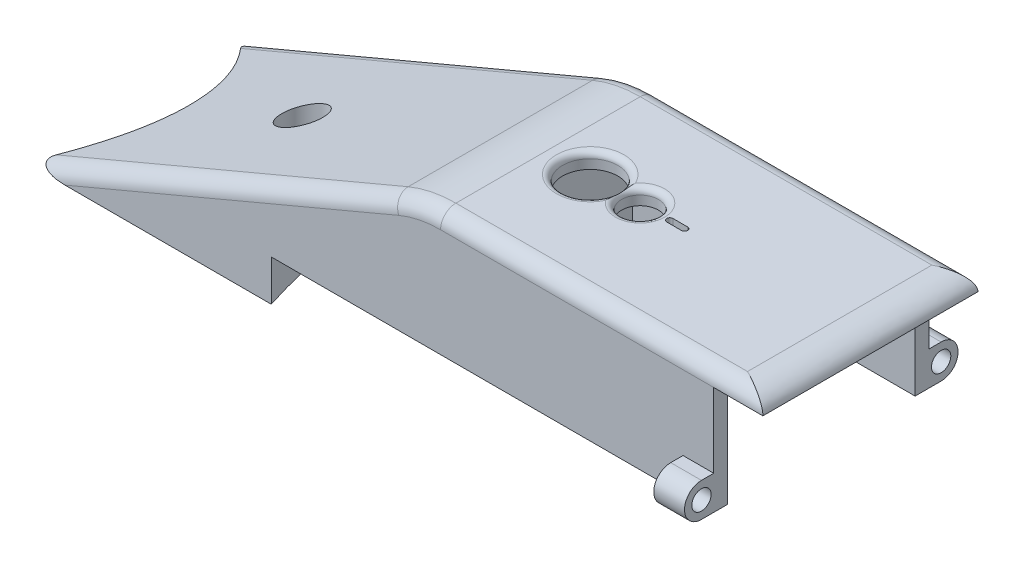
SolidWorks part; units mm, degrees
ref_plane "Front Plane" through (0, 0, 0) normal (0, 0, 1) x (1, 0, 0)
ref_plane "Top Plane" through (0, 0, 0) normal (0, 1, 0) x (1, 0, 0)
ref_plane "Right Plane" through (0, 0, 0) normal (1, 0, 0) x (0, 0, -1)
sketch "Sketch1" plane through (0, 0, 0) normal (0, 0, 1) x (1, 0, 0)
  line L0 (40.64, 72.2205) -> (-17.78, 72.2205)
  line L1 (-17.78, 72.2205) -> (-17.78, 49.8685)
  line L2 (40.64, 49.8685) -> (-50.8, 49.8685) construction
  line L5 (-20.955, 75.3955) -> (50.8, 75.3955)
  line L6 (50.8, 72.2205) -> (50.8, 60.0132) construction
  line L7 (50.8, 75.3955) -> (50.8, 72.2205)
  line L8 (50.8, 72.2205) -> (-17.78, 72.2205)
  line L14 (-101.6, 41.4018) -> (-50.8, 41.4018)
  line L15 (-50.8, 41.4018) -> (-50.8, 49.8685)
  line L16 (-50.8, 49.8685) -> (-17.78, 49.8685)
  line L17 (50.8, 41.4018) -> (-50.8, 41.4018) construction
  line L18 (-50.8, 49.8685) -> (-50.8, 41.4018) construction
  line L19 (-20.955, 75.3955) -> (-101.6, 41.4018)
  dimension "D1" = 3.175
  dimension "D2" = 68.58
  dimension "D3" = 3.175
  dimension "D4" = 50.8
extrude "Boss-Extrude1" add sketch "Sketch1" along normal mid plane 44.45
fillet "Fillet1" radius 25.4 1 edges at (-20.955, 75.3955, 0)
sketch "Sketch2" plane through (0, 72.2205, 0) normal (0, -1, 0) x (1, 0, 0)
  line L1 (-17.78, 22.225) -> (40.64, 22.225)
  line L2 (-17.78, 22.225) -> (-17.78, 19.389)
  line L3 (-17.78, 19.389) -> (40.64, 19.389)
  line L4 (40.64, 22.225) -> (40.64, 19.389)
  line L5 (-17.78, -22.225) -> (40.64, -22.225)
  line L6 (-17.78, -22.225) -> (-17.78, -19.389)
  line L7 (-17.78, -19.389) -> (40.64, -19.389)
  line L8 (40.64, -22.225) -> (40.64, -19.389)
  dimension "D1" = 2.836
sketch "Sketch3" plane through (-50.8, 0, 0) normal (1, 0, 0) x (0, 0, -1)
  arc A0 (-22.225, 41.4018) -> (22.225, 41.4018) centre (0, -6.598) cw
  dimension "D1" = 52.8955
extrude "Cut-Extrude1" cut sketch "Sketch3" against normal through all and the other way through all flip side to cut
extrude "Boss-Extrude2" add sketch "Sketch2" along normal up to surface (22.352 mm away)
fillet "Fillet2" radius 3.175 1 edges at (50.8, 75.3955, 0) second distance 6.35 first distance on face at (50.8, 73.808, 0)
sketch "Sketch4" plane through (0, 75.3955, 0) normal (0, 1, 0) x (1, 0, 0)
  line L0 (9.3436, 0) -> (12.3916, 0) construction
  line L2 (9.3436, 0.635) -> (12.3916, 0.635)
  line L3 (9.3436, -0.635) -> (12.3916, -0.635)
  circle A0 centre (-7.1109, 0) radius 5.715
  circle A1 centre (3.1891, 0) radius 3.81
  arc A2 (9.3436, 0.635) -> (9.3436, -0.635) centre (9.3436, 0) ccw
  arc A3 (12.3916, -0.635) -> (12.3916, 0.635) centre (12.3916, 0) ccw
  circle A4 centre (-7.1109, 0) radius 5 construction
  circle A5 centre (3.1891, 0) radius 3.25 construction
  arc A6 (9.3436, 0.5471) -> (9.3436, -0.5471) centre (9.3436, 0) ccw construction
  point P9 (10.8676, 0)
  dimension "D1" = 11.43
  dimension "D2" = 7.62
  dimension "D3" = 0.635
  dimension "D4" = 3.048
extrude "Cut-Extrude2" cut sketch "Sketch4" against normal up to surface (3.175 mm away) up to face at (29.845, 72.2205, 2.7781)
fillet "Fillet4" radius 1.27 2 edges at (3.1891, 75.3955, 3.81) (-7.1109, 75.3955, 5.715)
sketch "Sketch5" plane through (0, 75.3955, 0) normal (0, 1, 0) x (1, 0, 0)
  line L0 (-15.8204, 22.225) -> (-15.8204, -22.225) construction
  circle A0 centre (-66.6204, 0) radius 2.5
  dimension "D2" = 5
  dimension "D1" = 50.8
extrude "Cut-Extrude3" cut sketch "Sketch5" against normal through all
sketch "Sketch6" plane through (0, 75.3955, 0) normal (0, 1, 0) x (1, 0, 0)
  circle A0 centre (-66.6204, 0) radius 4.25
  dimension "D1" = 8.5
sketch "Sketch7" plane through (0, 49.8685, 0) normal (0, -1, 0) x (1, 0, 0)
  line L0 (-38.862, 0) -> (-26.162, 0) construction
  line L1 (-38.862, 5) -> (-26.162, 5)
  line L2 (-38.862, -5) -> (-26.162, -5)
  arc A0 (-38.862, 5) -> (-38.862, -5) centre (-38.862, 0) ccw
  arc A1 (-26.162, -5) -> (-26.162, 5) centre (-26.162, 0) ccw
  point P2 (-32.512, 0)
  dimension "D2" = 5
  dimension "D1" = 12.7
  dimension "D3" = 6.35
extrude "Cut-Extrude5" cut sketch "Sketch7" against normal blind 7
sketch "Sketch8" plane through (40.64, 0, 0) normal (1, 0, 0) x (0, 0, -1)
  line L0 (-22.225, 49.8685) -> (-24.765, 49.8685)
  line L1 (-24.765, 56.8685) -> (-22.225, 56.8685)
  line L2 (-22.225, 49.8685) -> (-22.225, 72.2205) construction
  line L4 (-22.225, 56.8685) -> (-22.225, 49.8685)
  line L5 (0, 0) -> (0, 55.9178) construction
  line L6 (22.225, 56.8685) -> (22.225, 49.8685)
  line L7 (24.765, 56.8685) -> (22.225, 56.8685)
  line L8 (22.225, 49.8685) -> (24.765, 49.8685)
  line L9 (22.225, 49.8685) -> (22.225, 72.2205) construction
  arc A0 (-24.765, 49.8685) -> (-24.765, 56.8685) centre (-24.765, 53.3685) cw
  circle A1 centre (-24.765, 53.3685) radius 2
  circle A3 centre (24.765, 53.3685) radius 2
  arc A4 (24.765, 49.8685) -> (24.765, 56.8685) centre (24.765, 53.3685) ccw
  dimension "D1" = 4
  dimension "D2" = 7
extrude "Boss-Extrude3" add sketch "Sketch8" against normal blind 6.35
fillet "Fillet3" radius 3.175 6 edges at (-20.8532, 74.8919, -22.225) (-63.6432, 57.4014, -22.225) (-63.6432, 57.4014, 22.225) (-20.8532, 74.8919, 22.225)
extrude "Cut-Extrude8" cut sketch "Sketch6" against normal blind 24.13
